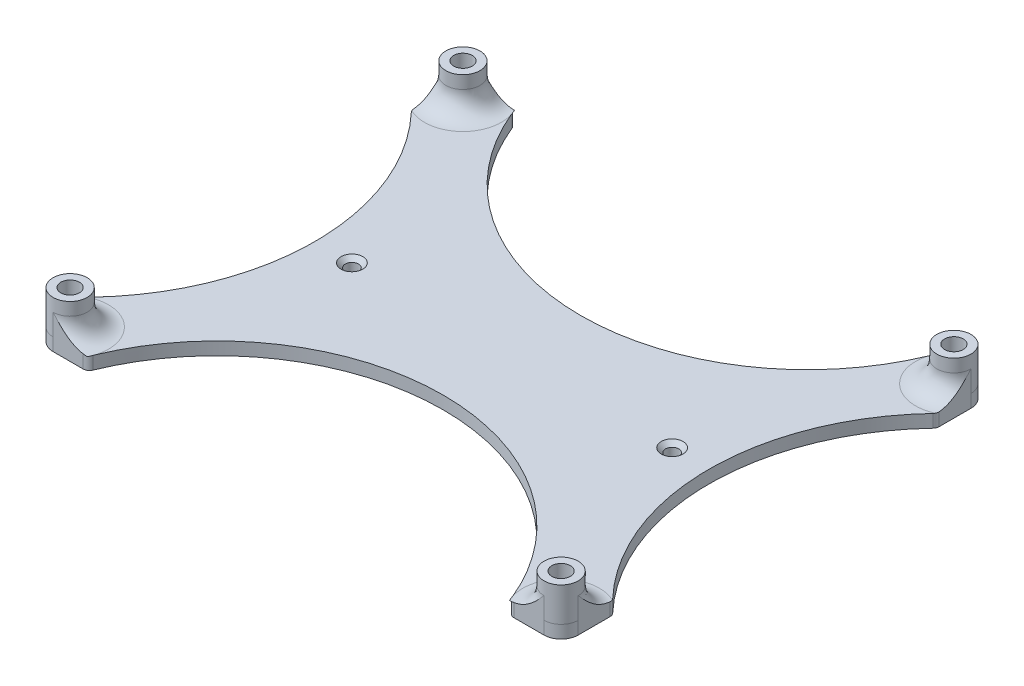
SolidWorks part; units mm, degrees
ref_plane "Alzado" through (0, 0, 0) normal (0, 0, 1) x (1, 0, 0)
ref_plane "Planta" through (0, 0, 0) normal (0, 1, 0) x (1, 0, 0)
ref_plane "Vista lateral" through (0, 0, 0) normal (1, 0, 0) x (0, 0, -1)
sketch "Croquis1" plane through (0, 0, 0) normal (0, 1, 0) x (1, 0, 0)
  line L1 (0, 0) -> (123, 0)
  line L2 (0, 0) -> (0, 100)
  line L3 (0, 100) -> (123, 100)
  line L4 (123, 0) -> (123, 100)
  dimension "D1" = 123
  dimension "D2" = 100
extrude "Saliente-Extruir1" add sketch "Croquis1" along normal blind 3
sketch "Croquis2" plane through (0, 3, 0) normal (0, 1, 0) x (1, 0, 0)
  line L0 (61.5, 100) -> (61.5, 0) construction
  line L1 (123, 100) -> (0, 100) construction
  line L2 (0, 0) -> (123, 0) construction
  line L3 (123, 0) -> (123, 100) construction
  line L4 (4, 4) -> (119, 4) construction
  line L5 (4, 4) -> (4, 96) construction
  line L6 (4, 96) -> (119, 96) construction
  line L7 (119, 4) -> (119, 96) construction
  line L8 (4, 4) -> (119, 96) construction
  line L9 (4, 96) -> (119, 4) construction
  circle A0 centre (4, 96) radius 4
  circle A1 centre (4, 4) radius 4
  circle A2 centre (119, 4) radius 4
  circle A3 centre (119, 96) radius 4
  point P6 (61.5, 50)
  dimension "D1" = 115
  dimension "D2" = 92
extrude "Saliente-Extruir2" add sketch "Croquis2" along normal blind 8
sketch "Croquis3" plane through (0, 11, 0) normal (0, 1, 0) x (1, 0, 0)
  circle A0 centre (4, 4) radius 4 construction
  circle A1 centre (4, 96) radius 4
  circle A2 centre (4, 96) radius 4
  arc A3 (123, 4) -> (119, 0) centre (119, 4) ccw construction
  arc A4 (119, 100) -> (123, 96) centre (119, 96) ccw construction
  circle A5 centre (4, 4) radius 4
  arc A6 (123, 4) -> (119, 0) centre (119, 4) ccw
  arc A7 (119, 100) -> (123, 96) centre (119, 96) ccw
  circle A8 centre (4, 96) radius 2.175
  circle A9 centre (119, 96) radius 2.175
  circle A10 centre (119, 4) radius 2.175
  circle A11 centre (4, 4) radius 2.175
  dimension "D2" = 4.35
  dimension "D1" = 0
extrude "Cortar-Extruir1" cut sketch "Croquis3" against normal blind 4.5 contours A8 | A9 | A10 | A11 region at (4, 11, -96) region at (119, 11, -96) region at (119, 11, -4) region at (4, 11, -4)
fillet "Redondeo1" radius 4 4 edges at (0, 1.5, -100) (123, 1.5, -100) (123, 1.5, 0) (0, 1.5, 0)
fillet "Redondeo2" radius 5 4 edges at (116.1716, 3, -6.8284) (116.1716, 3, -93.1716) (6.8284, 3, -93.1716) (6.8284, 3, -6.8284)
sketch "Croquis4" plane through (0, 3, 0) normal (0, 1, 0) x (1, 0, 0)
  line L0 (0, 50) -> (123, 50) construction
  line L1 (0, 87.9377) -> (0, 12.0623) construction
  line L2 (123, 12.0623) -> (123, 87.9377) construction
  circle A0 centre (24, 50) radius 1.55
  circle A1 centre (99, 50) radius 1.55
  dimension "D2" = 3.1
  dimension "D1" = 75
  dimension "D3" = 24
extrude "Cortar-Extruir2" cut sketch "Croquis4" against normal up to surface (3 mm away) up to face at (61.5, 0, -50)
sketch "Croquis5" plane through (0, 3, 0) normal (0, 1, 0) x (1, 0, 0)
  line L0 (0, 87.9377) -> (0, 12.0623)
  line L1 (12.0623, 100) -> (110.9377, 100)
  line L2 (61.5, 100) -> (61.5, 0) construction
  line L3 (12.0623, 0) -> (110.9377, 0) construction
  line L4 (0, 50) -> (123, 50) construction
  line L5 (123, 12.0623) -> (123, 87.9377) construction
  line L6 (123, 87.9377) -> (123, 12.0623)
  line L7 (12.0623, 0) -> (110.9377, 0)
  arc A0 (12.0623, 100) -> (110.9377, 100) centre (61.5, 119.1195) ccw
  arc A1 (0, 87.9377) -> (0, 12.0623) centre (-39.2296, 50) cw
  arc A2 (123, 87.9377) -> (123, 12.0623) centre (162.2296, 50) ccw
  arc A3 (12.0623, 0) -> (110.9377, 0) centre (61.5, -19.1195) cw
extrude "Cortar-Extruir3" cut sketch "Croquis5" against normal up to surface (3 mm away) up to face at (24, 0, -51.55)
fillet "Redondeo3" radius 1.5 8 edges at (12.0623, 1.5, -100) (0, 1.5, -87.9377) (0, 1.5, -12.0623) (12.0623, 1.5, 0) (110.9377, 1.5, 0) (123, 1.5, -12.0623) (110.9377, 1.5, -100) (123, 1.5, -87.9377)
chamfer "Chaflán1" distance 1 angle 45 2 edges at (99, 3, -48.45) (24, 3, -48.45)
